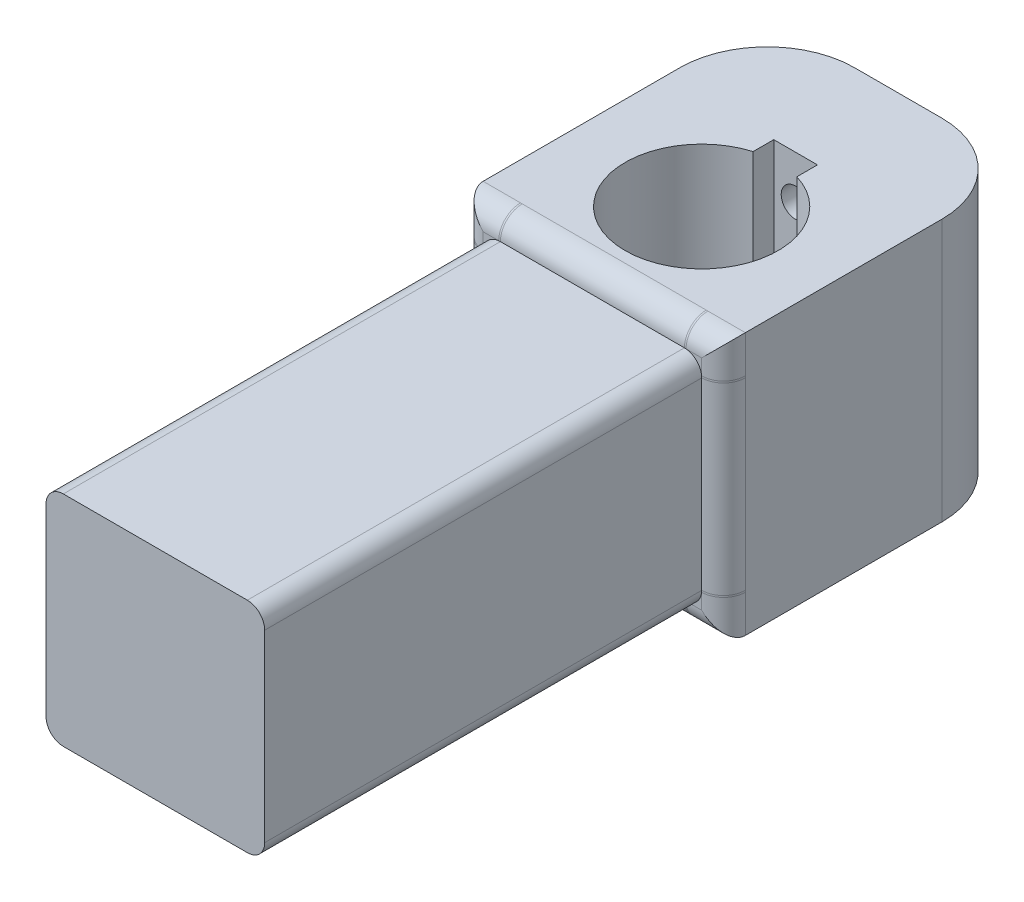
SolidWorks part; units mm, degrees
note: The reader was unsure of these and kept them because the rebuilt part matched: shared geometry of "Sketch3<7>".
ref_plane "Front Plane" through (0, 0, 0) normal (0, 0, 1) x (1, 0, 0)
ref_plane "Top Plane" through (0, 0, 0) normal (0, 1, 0) x (1, 0, 0)
ref_plane "Right Plane" through (0, 0, 0) normal (1, 0, 0) x (0, 0, -1)
sketch "Sketch1" plane through (0, 0, 0) normal (0, 0, 1) x (1, 0, 0)
  line L0 (25.019, 21.0502) -> (25.019, -21.0503)
  line L1 (21.0503, -25.019) -> (-21.0503, -25.019)
  line L2 (-25.019, -21.0503) -> (-25.019, 21.0502)
  line L3 (-21.0502, 25.019) -> (21.0502, 25.019)
  arc A0 (25.019, -21.0503) -> (21.0503, -25.019) centre (21.0503, -21.0503) cw
  arc A1 (-21.0503, -25.019) -> (-25.019, -21.0503) centre (-21.0503, -21.0503) cw
  arc A2 (-25.019, 21.0502) -> (-21.0502, 25.019) centre (-21.0503, 21.0502) cw
  arc A3 (21.0502, 25.019) -> (25.019, 21.0502) centre (21.0502, 21.0502) cw
extrude "Boss-Extrude1" add sketch "Sketch1" along normal blind 100
sketch "Sketch2" plane through (0, 0, 0) normal (0, 0, 1) x (1, 0, 0)
  line L1 (30, -30) -> (-30, -30)
  line L2 (30, -30) -> (30, 30)
  line L3 (30, 30) -> (-30, 30)
  line L4 (-30, -30) -> (-30, 30)
  line L5 (30, -30) -> (-30, 30) construction
  line L6 (30, 30) -> (-30, -30) construction
  point P0 (0, 0)
  dimension "D1" = 60
  dimension "D2" = 60
extrude "Boss-Extrude2" add sketch "Sketch2" against normal blind 70
sketch "Sketch3" plane through (0, -30, 0) normal (0, -1, 0) x (1, 0, 0)
  line L0 (-21.0503, 0) -> (21.0502, 0) construction
  line L6 (-5, -46.5) -> (5, -46.5)
  line L7 (-5, -46.5) -> (-5, -38.5)
  line L8 (-5, -38.5) -> (5, -38.5)
  line L9 (5, -46.5) -> (5, -38.5)
  line L10 (-5, -46.5) -> (5, -38.5) construction
  line L11 (-5, -38.5) -> (5, -46.5) construction
  circle A0 centre (0, -25) radius 17.5
  point P2 (0, -7.5)
  point P9 (0, -42.5)
  dimension "D1" = 35
  dimension "D2" = 25
  dimension "D3" = 10
  dimension "D4" = 8
extrude "Cut-Extrude2" cut sketch "Sketch3" against normal blind 60 contours L9 A0 L7 L8 | L7 A0 L9 L8
extrude "Cut-Extrude3" cut sketch "Sketch3<7>" against normal blind 60 contours A0 L7 L6 L9
sketch "Sketch3<7>" plane through (0, -30, 0) normal (0, -1, 0) x (1, 0, 0) same geometry as "Sketch3"
hole_wizard "M6 Clearance Hole1" positions "Sketch5" profile "Sketch7" hole size "M6" standard "ANSI Metric"
sketch "Sketch5" plane through (0, 0, -70) normal (0, 0, -1) x (-1, 0, 0)
  line L0 (30, -30) -> (-30, -30) construction
  line L1 (-30, 30) -> (30, 30) construction
  point P0 (0, 20)
  point P2 (0, 0)
  point P5 (0, -20)
  point P12 (0, 0)
  point P13 (0, 0)
  point P17 (0, -30)
  dimension "D1" = 10
  dimension "D2" = 10
sketch "Sketch7" plane through (0, 20, -70) normal (1, 0, 0) x (0, 1, 0)
  line L0 (0, 0) -> (0, 25.4818)
  line L1 (0, 25.4818) -> (3.3, 23.499)
  line L2 (3.3, 23.499) -> (3.3, 0)
  line L5 (3.3, 0) -> (0, 0)
  line L10 (0, 25.4818) -> (-3.3, 23.499) construction
  line L11 (0, -6.35) -> (0, 107.95) construction
  dimension "Hole Dia." = 6.6
  dimension "Hole Depth" = 23.499
  dimension "Drill Angle" = 118
fillet "Fillet1" radius 20 2 edges at (-30, 0, -70) (30, 0, -70)
fillet "Fillet2" radius 5 4 edges at (0, 30, 0) (0, -30, 0) (30, 0, 0) (-30, 0, 0)
